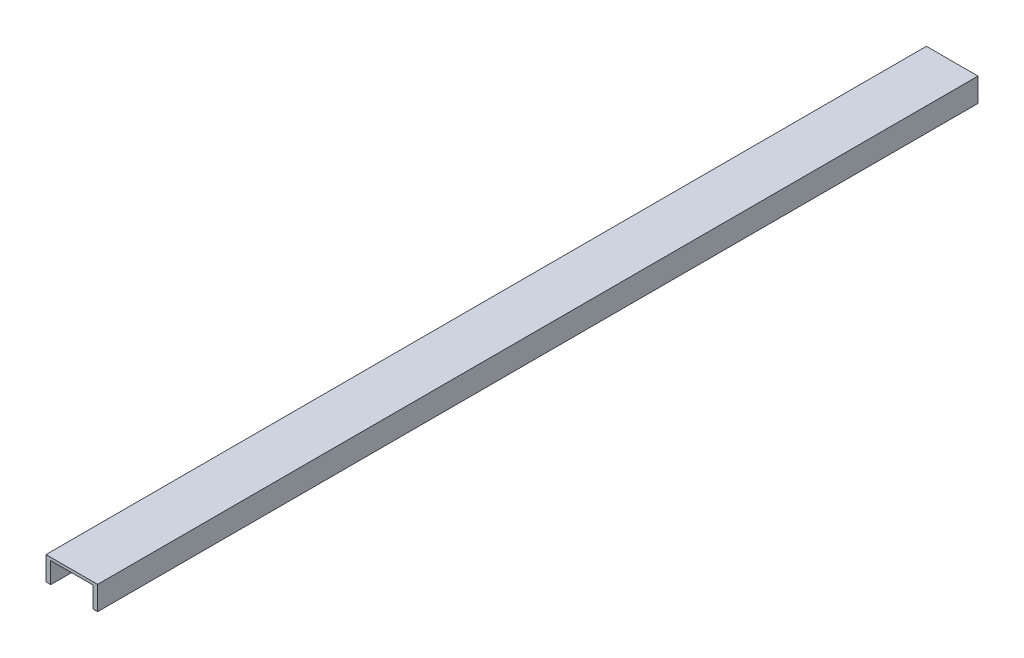
SolidWorks part; units mm, degrees
material "AISI 4340 Acero normalizado"
ref_plane "Alzado" through (0, 0, 0) normal (0, 0, 1) x (1, 0, 0)
ref_plane "Planta" through (0, 0, 0) normal (0, 1, 0) x (1, 0, 0)
ref_plane "Vista lateral" through (0, 0, 0) normal (1, 0, 0) x (0, 0, -1)
sketch "Croquis2" plane through (0, 0, 0) normal (0, 0, 1) x (1, 0, 0)
  line L0 (31.1, -17.5) -> (31.1, 13.2)
  line L1 (38.1, -17.5) -> (-38.1, -17.5)
  line L2 (38.1, -17.5) -> (38.1, 17.5)
  line L3 (38.1, 17.5) -> (-38.1, 17.5)
  line L4 (-38.1, -17.5) -> (-38.1, 17.5)
  line L5 (38.1, -17.5) -> (-38.1, 17.5) construction
  line L6 (38.1, 17.5) -> (-38.1, -17.5) construction
  line L7 (31.1, 13.2) -> (-31.1, 13.2)
  line L8 (-31.1, -17.5) -> (-31.1, 13.2)
  line L11 (31.1, -17.5) -> (-31.1, -17.5)
  point P0 (0, 0)
  dimension "D1" = 35
  dimension "D2" = 76.2
  dimension "D3" = 4.3
  dimension "D4" = 7
  dimension "D5" = 7
extrude "Saliente-Extruir1" add sketch "Croquis2" along normal mid plane 1300 contours L1 L8 L7 L0 L2 L3 L4 region at (31.9385, -2.15, 0)
